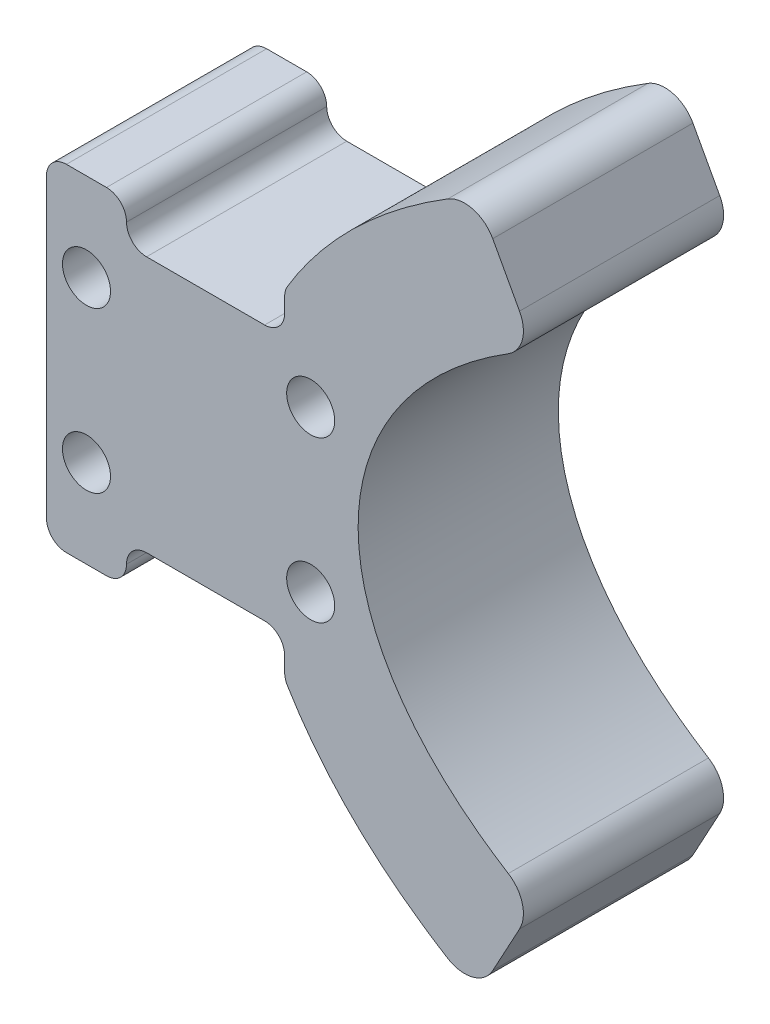
SolidWorks part; units mm, degrees
ref_plane "Front Plane" through (0, 0, 0) normal (0, 0, 1) x (1, 0, 0)
ref_plane "Top Plane" through (0, 0, 0) normal (0, 1, 0) x (1, 0, 0)
ref_plane "Right Plane" through (0, 0, 0) normal (1, 0, 0) x (0, 0, -1)
sketch "Sketch2" plane through (0, 0, 0) normal (0, 0, 1) x (1, 0, 0)
  line L0 (-65, 0) -> (65, 0) construction
  line L1 (-42.9935, 30) -> (42.9935, 30) construction
  line L2 (-42.9935, -30) -> (42.9935, -30) construction
  line L3 (-44.845, 33.4117) -> (-48.1898, 39.5749)
  line L4 (0, 0) -> (0, 55) construction
  line L5 (42.9935, 30) -> (50.1488, 43.1845)
  line L6 (42.9935, -30) -> (50.1488, -43.1845)
  line L7 (-44.845, -33.4117) -> (-48.1894, -39.5741)
  line L8 (-78.0697, 12.2779) -> (-63.7772, 7.7221) construction
  circle A0 centre (-70.9235, 10) radius 3
  circle A1 centre (-70.9235, -10) radius 3
  arc A2 (-46.2454, -28.1087) -> (-44.845, -33.4117) centre (-48.3606, -31.5037) cw
  arc A3 (-46.2454, 28.1087) -> (-44.845, 33.4117) centre (-48.3606, 31.5037) ccw
  arc A4 (-53.8006, -41.0733) -> (-48.1894, -39.5741) centre (-51.705, -37.6662) ccw
  arc A5 (-48.1898, 39.5749) -> (-53.8007, 41.0743) centre (-51.7054, 37.6669) ccw
  ellipse E0 centre (0, 0) end of major axis (-65, 0) minor radius 40 (-46.2454, 28.1087) -> (-46.2454, -28.1087) ccw
  ellipse E1 centre (0, 0) end of major axis (-65, 0) minor radius 40 (42.9935, -30) -> (42.9935, 30) ccw
  spline S0 degree 3 poles (50.1488, -43.1845) (51.3994, -42.5053) (56.4654, -39.5769) (64.55, -33.5541) (72.9491, -23.9791) (78.6267, -12.6315) (80.6864, -0.0005) (78.6269, 12.6306) (72.9495, 23.9783) (64.5507, 33.5535) (56.4659, 39.5766) (51.3997, 42.5052) (50.1488, 43.1845) knots 8.576734 8.576734 8.576734 8.576734 8.63938 8.835729 9.032079 9.228428 9.424778 9.621128 9.817477 10.013827 10.210176 10.272835 10.272835 10.272835 10.272835
  spline S1 degree 3 poles (-53.8007, 41.0743) (-54.4877, 40.6518) (-58.2022, 38.2846) (-65.0574, 32.9774) (-72.9501, 23.9797) (-78.6277, 12.6321) (-80.6875, 0.001) (-78.628, -12.63) (-72.9506, -23.9777) (-64.5517, -33.5529) (-57.572, -38.7528) (-53.8086, -41.0684) (-53.8006, -41.0733) knots 5.497384 5.497384 5.497384 5.497384 5.533298 5.694137 5.890486 6.086836 6.283185 6.479535 6.675884 6.872234 7.068583 7.069002 7.069002 7.069002 7.069002
  point P20 (-70.9235, 10)
  dimension "D6" = 6
  dimension "D8" = 4
  dimension "D1" = 80
  dimension "D2" = 130
  dimension "D3" = 30
  dimension "D7" = 10
extrude "Boss-Extrude1" add sketch "Sketch2" along normal blind 25 contours L3 S1 L7 E0 region at (-45.3695, 30.7138, 0)
sketch "Sketch3" plane through (0, 0, 25) normal (0, 0, 1) x (1, 0, 0)
  line L0 (-74.1773, 21) -> (-103.9266, 21)
  line L1 (-103.9266, 21) -> (-103.9266, -21)
  line L2 (-103.9266, -21) -> (-74.1766, -21)
  line L3 (-65, 0) -> (-30.8049, 0) construction
  ellipse E0 centre (0, 0) end of major axis (-65, 0) minor radius 40 (-46.2454, 28.1087) -> (-46.2454, -28.1087) ccw construction
  spline S0 degree 3 poles (-1837.369, -815.7854) (546.5954, -144.4125) (61.1265, 130.6665) (-65.0574, 32.9774) (-72.9501, 23.9797) (-78.6277, 12.6321) (-80.6875, 0.001) (-78.628, -12.63) (-72.9506, -23.9777) (-64.5517, -33.5529) (71.6379, -135.0144) (593.7163, 180.3306) (-1773.1527, 919.2648) knots -1.345322 -1.345322 -1.345322 -1.345322 5.533298 5.694137 5.890486 6.086836 6.283185 6.479535 6.675884 6.872234 7.068583 14.346498 14.346498 14.346498 14.346498 only from (-53.8007, 41.0743) to (-53.8006, -41.0733) construction
  spline S1 degree 3 poles (-74.1773, 21) (-75.756, 18.2821) (-78.8003, 11.5738) (-80.6875, 0.001) (-78.8004, -11.5725) (-75.7557, -18.2815) (-74.1766, -21) knots 5.93984 5.93984 5.93984 5.93984 6.086836 6.283185 6.479535 6.626566 6.626566 6.626566 6.626566
  dimension "D1" = 29.75
  dimension "D2" = 21
  dimension "D3" = 21
extrude "Boss-Extrude2" add sketch "Sketch3" against normal up to surface (25 mm away) up to face at (-67.9235, -10, 0)
sketch "Sketch4" plane through (0, 0, 25) normal (0, 0, 1) x (1, 0, 0)
  line L0 (-93.9235, 21) -> (-93.9235, 16)
  line L2 (-67.9235, 16) -> (-91.4235, 16) construction
  line L3 (-93.9235, 16) -> (-74.1773, 16)
  line L4 (-74.1773, 16) -> (-74.1773, 21)
  line L5 (-74.1766, -21) -> (-74.1766, -16)
  line L6 (-91.4235, -16) -> (-67.9235, -16) construction
  line L7 (-74.1766, -16) -> (-93.9235, -16)
  line L8 (-93.9235, -16) -> (-93.9235, -21)
  line L9 (-103.9266, -21) -> (-74.1766, -21) construction
  line L10 (-93.9235, -21.6324) -> (-93.9235, -18.5) construction
  line L11 (-93.9235, -21) -> (-74.1766, -21)
  line L12 (-93.9235, 21) -> (-74.1773, 21)
extrude "Cut-Extrude1" cut sketch "Sketch4" against normal through all
fillet "Fillet1" radius 2.5 10 edges at (-93.9235, 16, 12.5) (-93.9235, 21, 12.5) (-103.9266, -21, 12.5) (-93.9235, -21, 12.5) (-93.9235, -16, 12.5) (-74.1766, -16, 12.5) (-74.1766, -21, 12.5) (-74.1773, 21, 12.5) (-74.1773, 16, 12.5) (-103.9266, 21, 12.5)
sketch "Sketch5" plane through (0, 0, 25) normal (0, 0, 1) x (1, 0, 0)
  circle A0 centre (-98.9235, 10) radius 3
  circle A1 centre (-98.9235, -10) radius 3
  circle A2 centre (-70.9235, 10) radius 3 construction
extrude "Cut-Extrude2" cut sketch "Sketch5" against normal through all
